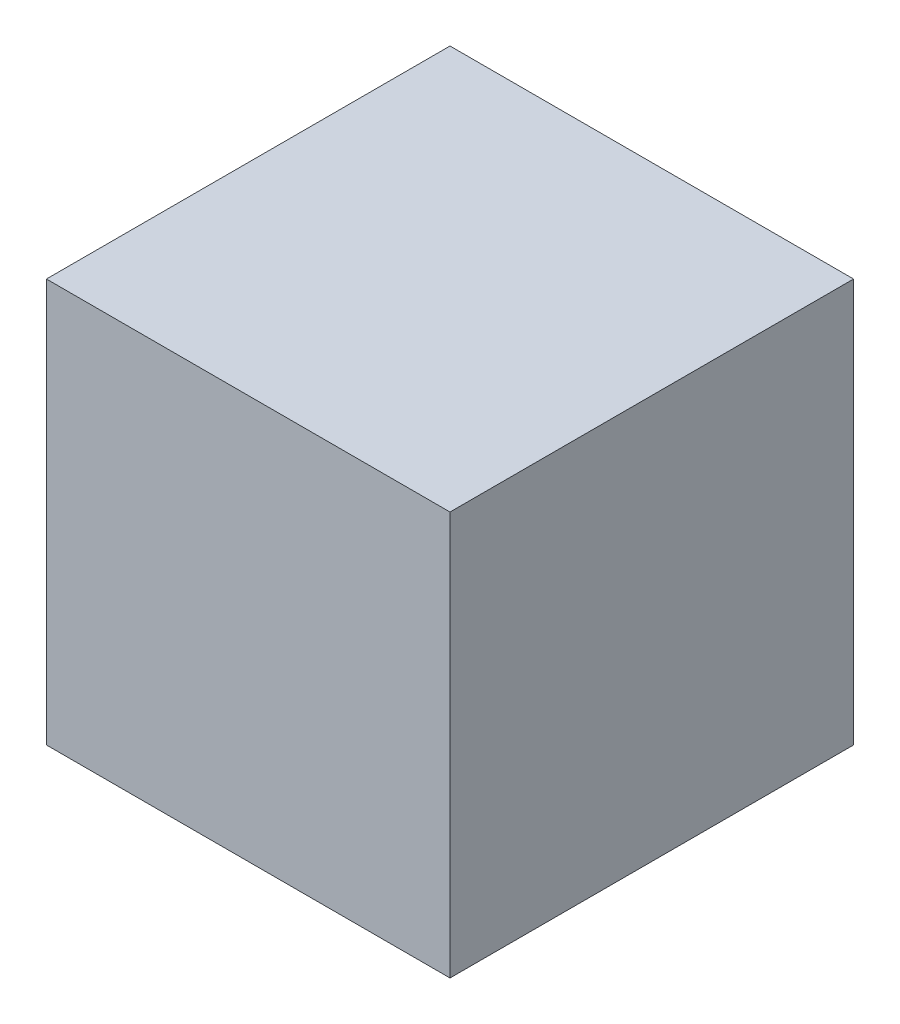
SolidWorks part; units mm, degrees
ref_plane "Front Plane" through (0, 0, 0) normal (0, 0, 1) x (1, 0, 0)
ref_plane "Top Plane" through (0, 0, 0) normal (0, 1, 0) x (1, 0, 0)
ref_plane "Right Plane" through (0, 0, 0) normal (1, 0, 0) x (0, 0, -1)
ref_plane "Plane1" through (0, 0, 1000) normal (0, 0, 1) x (1, 0, 0)
sketch "Sketch1" plane through (0, 0, 1000) normal (0, 0, 1) x (1, 0, 0)
  line L0 (0, 1000) -> (3013.077, 1000) construction
  line L2 (750, 1250) -> (1250, 1250)
  line L3 (750, 1250) -> (750, 750)
  line L4 (750, 750) -> (1250, 750)
  line L5 (1250, 1250) -> (1250, 750)
  point P6 (1000, 750)
  point P8 (1250, 685.7461)
  point P9 (750, 1000)
  dimension "D1" = 500
  dimension "D2" = 1000
  dimension "D3" = 1000
extrude "Boss-Extrude1" add sketch "Sketch1" along normal blind 250 and the other way blind 250 contours L3 L4 L5 L2
